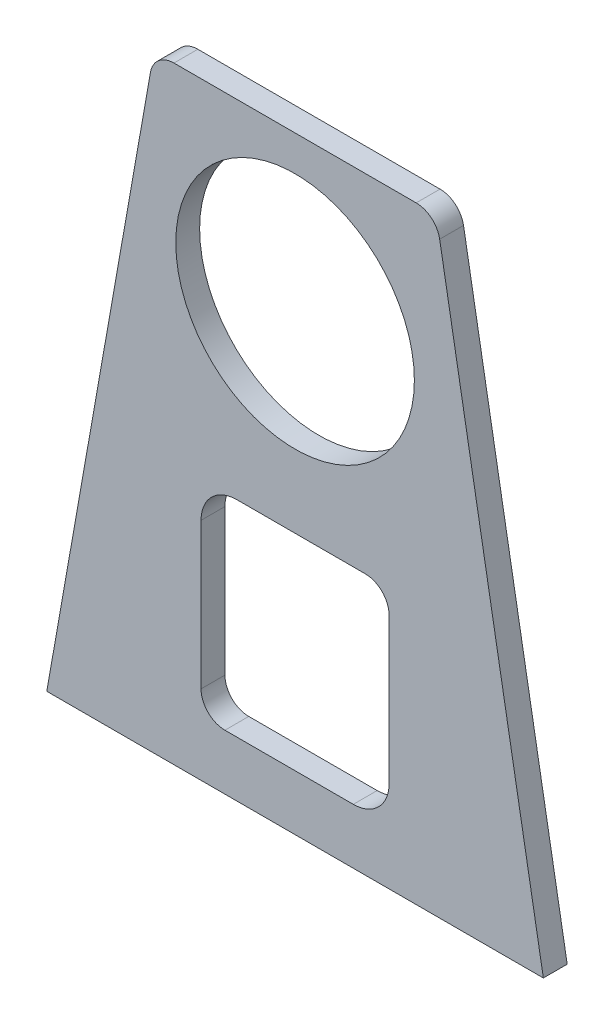
SolidWorks part; units mm, degrees
ref_plane "Front" through (0, 0, 0) normal (0, 0, 1) x (1, 0, 0)
ref_plane "Top" through (0, 0, 0) normal (0, 1, 0) x (1, 0, 0)
ref_plane "Right" through (0, 0, 0) normal (1, 0, 0) x (0, 0, -1)
sketch "Sketch3" plane through (0, 0, 0) normal (0, 0, 1) x (1, 0, 0)
  line L0 (-460.0059, 0) -> (580.5937, 0)
  line L1 (580.5937, 0) -> (363.3233, 1232.202)
  line L3 (-242.7354, 1232.202) -> (-460.0059, 0)
  line L4 (60.2939, 0) -> (60.2939, 1273.5196) construction
  line L11 (-86.7347, 116.0597) -> (182.3225, 116.0597)
  line L15 (-136.7347, 166.0597) -> (-136.7347, 471.9705)
  line L16 (-61.7347, 546.9705) -> (207.3225, 546.9705)
  line L17 (-193.4951, 1273.5196) -> (314.0829, 1273.5196)
  line L18 (257.3225, 191.0597) -> (257.3225, 496.9705)
  line L19 (-136.7347, 116.0597) -> (257.3225, 546.9705) construction
  line L20 (-136.7347, 546.9705) -> (257.3225, 116.0597) construction
  arc A10 (-242.7354, 1232.202) -> (-193.4951, 1273.5196) centre (-193.4951, 1223.5196) cw
  arc A11 (363.3233, 1232.202) -> (314.0829, 1273.5196) centre (314.0829, 1223.5196) ccw
  circle A13 centre (60.2939, 949.6019) radius 250
  arc A14 (-136.7347, 471.9705) -> (-61.7347, 546.9705) centre (-61.7347, 471.9705) cw
  arc A15 (182.3225, 116.0597) -> (257.3225, 191.0597) centre (182.3225, 191.0597) ccw
  arc A16 (-86.7347, 116.0597) -> (-136.7347, 166.0597) centre (-86.7347, 166.0597) cw
  arc A17 (257.3225, 496.9705) -> (207.3225, 546.9705) centre (207.3225, 496.9705) ccw
  point P11 (60.2939, 331.5151)
  point P28 (-235.45, 1273.5196)
  point P33 (356.0379, 1273.5196)
  dimension "D4" = 500
  dimension "D5" = 75
  dimension "D6" = 75
  dimension "D7" = 50
  dimension "D8" = 50
  dimension "D9" = 50
  dimension "D11" = 50
  dimension "D2" = 80
  dimension "D3" = 80
extrude "Boss-Extrude1" add sketch "Sketch3" along normal blind 50 contours L3 L0 L1 region at (-335.1745, 613.2452, 0)
